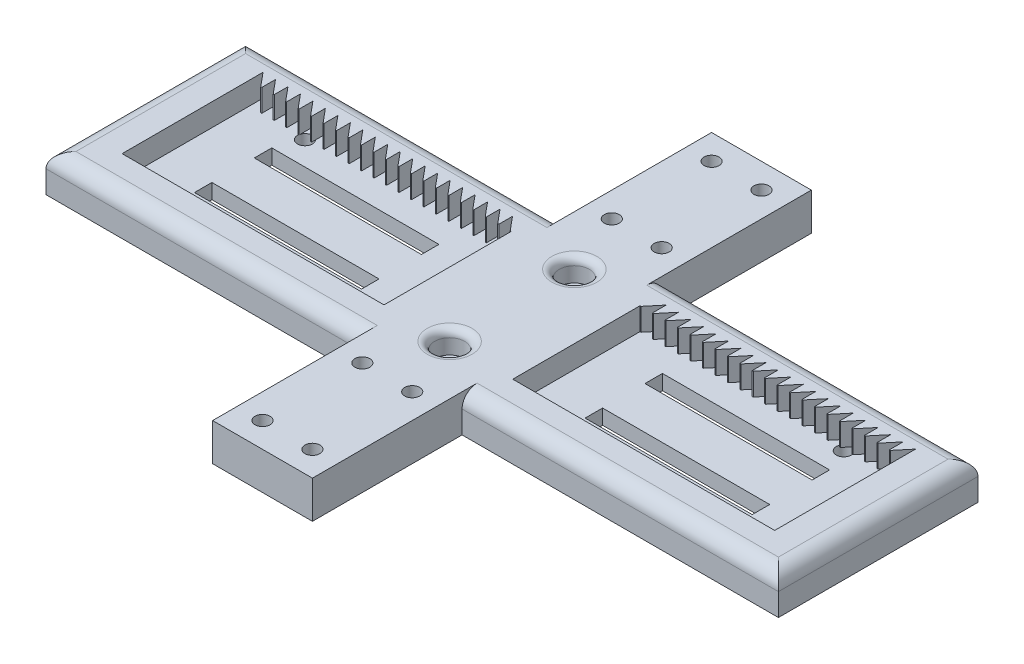
SolidWorks part; units mm, degrees
ref_plane "Front Plane" through (0, 0, 0) normal (0, 0, 1) x (1, 0, 0)
ref_plane "Top Plane" through (0, 0, 0) normal (0, 1, 0) x (1, 0, 0)
ref_plane "Right Plane" through (0, 0, 0) normal (1, 0, 0) x (0, 0, -1)
sketch "Sketch2" plane through (0, 0, 0) normal (0, 1, 0) x (1, 0, 0)
  line L0 (-12.9, 12.5) -> (-15.4, 15.5)
  line L2 (-73.4, 20) -> (-73.4, -20)
  line L5 (-65.4, 12.75) -> (-12.9, 12.75)
  line L6 (-65.4, 12.75) -> (-65.4, -12.75)
  line L7 (-65.4, -12.75) -> (-12.9, -12.75)
  line L8 (-12.9, 12.75) -> (-12.9, -12.75)
  line L9 (-73.4, 0) -> (-65.4, 0) construction
  line L10 (-15.4, 15.5) -> (-15.4, 12.5)
  line L11 (-15.4, 12.5) -> (-17.9, 15.5)
  line L12 (-17.9, 15.5) -> (-17.9, 12.5)
  line L13 (-17.9, 12.5) -> (-20.4, 15.5)
  line L14 (-20.4, 15.5) -> (-20.4, 12.5)
  line L15 (-20.4, 12.5) -> (-22.9, 15.5)
  line L16 (-22.9, 15.5) -> (-22.9, 12.5)
  line L17 (-22.9, 12.5) -> (-25.4, 15.5)
  line L18 (-25.4, 15.5) -> (-25.4, 12.5)
  line L19 (-25.4, 12.5) -> (-27.9, 15.5)
  line L20 (-27.9, 15.5) -> (-27.9, 12.5)
  line L21 (-27.9, 12.5) -> (-30.4, 15.5)
  line L22 (-30.4, 15.5) -> (-30.4, 12.5)
  line L23 (-30.4, 12.5) -> (-32.9, 15.5)
  line L24 (-32.9, 15.5) -> (-32.9, 12.5)
  line L25 (-32.9, 12.5) -> (-35.4, 15.5)
  line L26 (-35.4, 15.5) -> (-35.4, 12.5)
  line L27 (-35.4, 12.5) -> (-37.9, 15.5)
  line L28 (-37.9, 15.5) -> (-37.9, 12.5)
  line L29 (-37.9, 12.5) -> (-40.4, 15.5)
  line L30 (-40.4, 15.5) -> (-40.4, 12.5)
  line L31 (-40.4, 12.5) -> (-42.9, 15.5)
  line L32 (-42.9, 15.5) -> (-42.9, 12.5)
  line L33 (-42.9, 12.5) -> (-45.4, 15.5)
  line L34 (-45.4, 15.5) -> (-45.4, 12.5)
  line L35 (-45.4, 12.5) -> (-47.9, 15.5)
  line L36 (-47.9, 15.5) -> (-47.9, 12.5)
  line L37 (0, 0) -> (0, 9.3891) construction
  line L38 (0, -20) -> (0, 20)
  line L39 (-52.9, -12.75) -> (-52.9, -5.7094) construction
  line L41 (-25.4, 12.75) -> (-25.4, -12.75) construction
  line L45 (3.0979, 0) -> (12.9, 0) construction
  line L46 (-47.9, 12.5) -> (-50.4, 15.5)
  line L47 (-50.4, 15.5) -> (-50.4, 12.5)
  line L48 (-50.4, 12.5) -> (-52.9, 15.5)
  line L49 (-52.9, 15.5) -> (-52.9, 12.5)
  line L50 (-52.9, 12.5) -> (-55.4, 15.5)
  line L51 (-55.4, 15.5) -> (-55.4, 12.5)
  line L52 (-55.4, 12.5) -> (-57.9, 15.5)
  line L53 (-57.9, 15.5) -> (-57.9, 12.5)
  line L54 (-57.9, 12.5) -> (-60.4, 15.5)
  line L55 (-60.4, 15.5) -> (-60.4, 12.5)
  line L56 (-60.4, 12.5) -> (-62.9, 15.5)
  line L57 (-62.9, 15.5) -> (-62.9, 12.5)
  line L58 (-62.9, 12.5) -> (-65.4, 15.5)
  line L59 (-65.4, 15.5) -> (-65.4, 12.5)
  line L60 (-73.4, 20) -> (0, 20)
  line L61 (-73.4, -20) -> (0, -20)
  line L74 (0, 20) -> (0, -20) construction
  line L75 (-12.9, 0) -> (0, 0) construction
  line L76 (0, 0) -> (12.9, 0) construction
  point P5 (-73.4, 0)
  dimension "D2" = 40
  dimension "D3" = 12.5
  dimension "D4" = 25.4
  dimension "D5" = 12.5
  dimension "D6" = 2.5
  dimension "D7" = 3
  dimension "D8" = 25.5
  dimension "D9" = 12.5
  dimension "D10" = 8
  dimension "D11" = 52.9
  dimension "D15" = 21
extrude "Boss-Extrude1" add sketch "Sketch2" against normal blind 3 contours L2 L61 L38 L60
extrude "Boss-Extrude2" add sketch "Sketch2<3>" along normal blind 4.5
sketch "Sketch2<3>" plane through (0, 0, 0) normal (0, 1, 0) x (1, 0, 0) same geometry as "Sketch2"
sketch "Sketch3" plane through (0, 0, 0) normal (0, 1, 0) x (1, 0, 0)
  line L0 (-65.4, 15.5) -> (-65.4, -12.75) construction
  line L1 (-65.4, 7.75) -> (50.52, 7.75)
  line L2 (-65.4, 7.75) -> (-65.4, 4.25)
  line L3 (-65.4, 4.25) -> (50.52, 4.25)
  line L4 (50.52, 7.75) -> (50.52, 4.25)
  line L6 (-65.4, 0) -> (-44.0832, 0) construction
  line L7 (-55.9, 4.25) -> (-55.9, 7.75)
  line L8 (-22.4, 4.25) -> (-22.4, 7.75)
  line L9 (-12.9, 12.75) -> (-12.9, -12.75) construction
  line L10 (-7.44, 4.25) -> (-7.44, -3.7317) construction
  line L11 (-22.4, -4.25) -> (-22.4, -7.75)
  line L12 (-55.9, -4.25) -> (-55.9, -7.75)
  line L13 (-65.4, -4.25) -> (50.52, -4.25)
  line L14 (50.52, -7.75) -> (50.52, -4.25)
  line L15 (-65.4, -7.75) -> (50.52, -7.75)
  line L16 (-65.4, -7.75) -> (-65.4, -4.25)
  line L17 (7.52, -4.25) -> (7.52, -7.75)
  line L18 (41.02, -4.25) -> (41.02, -7.75)
  line L19 (41.02, 4.25) -> (41.02, 7.75)
  line L20 (7.52, 4.25) -> (7.52, 7.75)
  line L21 (-65.4, 15.5) -> (-65.4, -12.75) construction
  line L22 (-65.4, 15.5) -> (-65.4, -12.75)
  point P10 (-65.4, 6)
  dimension "D1" = 3.5
  dimension "D2" = 6
  dimension "D3" = 9.5
  dimension "D4" = 9.5
extrude "Cut-Extrude1" cut sketch "Sketch3" against normal through all contours L3 L8 L1 L7 | L12 L15 L11 L13 | L20 L3 L19 L1 | L18 L13 L17 L15 region at (-39.15, 0, -6) region at (24.27, 0, -6) region at (-39.15, 0, 6) region at (24.27, 0, 6)
sketch "Sketch4" plane through (0, 4.5, 0) normal (0, 1, 0) x (1, 0, 0)
  line L2 (0, 12.5) -> (0, 0) construction
  circle A0 centre (0, 12.5) radius 1.75
  circle A2 centre (54, 12.5) radius 1.75
  circle A3 centre (54, -12.5) radius 1.75
  circle A4 centre (0, -12.5) radius 1.75
  dimension "D1" = 3.5
  dimension "D2" = 2
  dimension "D3" = 12.5
  dimension "D4" = 2
extrude "Cut-Extrude3" cut sketch "Sketch4" against normal through all contours A0 | A4 | A3 | A2
sketch "Sketch5" plane through (0, 4.5, 0) normal (0, 1, 0) x (1, 0, 0)
  circle A1 centre (0, 12.5) radius 3
  circle A4 centre (0, -12.5) radius 3
extrude "Cut-Extrude4" cut sketch "Sketch5" against normal offset from surface (4.5 mm away) 3 up to face at (-39.15, -3, 6)
sketch "Sketch7" plane through (0, -3, 0) normal (0, -1, 0) x (1, 0, 0)
  circle A0 centre (-54, 12.5) radius 1.5
  circle A1 centre (-54, -12.5) radius 1.5
  arc A2 (0, -10.75) -> (0, -14.25) centre (0, -12.5) ccw construction
  arc A3 (0, 14.25) -> (0, 10.75) centre (0, 12.5) ccw construction
  arc A4 (0, -10.75) -> (0, -14.25) centre (0, -12.5) ccw
  arc A5 (0, 14.25) -> (0, 10.75) centre (0, 12.5) ccw
  point P11 (0, 0)
  point P12 (0, 0)
  dimension "D1" = 3
  dimension "D2" = 3
  dimension "D3" = 54
extrude "Cut-Extrude5" cut sketch "Sketch7" against normal blind 3 contours A0 | A1
sketch "Sketch9" plane through (0, 4.5, 0) normal (0, 1, 0) x (1, 0, 0)
  line L1 (0, 20) -> (-10, 20)
  line L2 (0, 20) -> (0, 50)
  line L3 (0, 50) -> (-10, 50)
  line L4 (-10, 20) -> (-10, 50)
  line L5 (0, -20) -> (-10, -20)
  line L6 (0, -20) -> (0, -50)
  line L7 (0, -50) -> (-10, -50)
  line L8 (-10, -20) -> (-10, -50)
  dimension "D1" = 30
  dimension "D2" = 30
  dimension "D3" = 10
  dimension "D4" = 10
extrude "Boss-Extrude3" add sketch "Sketch9" against normal up to surface (7.5 mm away) up to face at (-54, -3, 11)
sketch "Sketch10" plane through (0, 4.5, 0) normal (0, 1, 0) x (1, 0, 0)
  line L0 (0, 15.5) -> (0, 50) construction
  line L1 (0, 0) -> (-6.4734, 0) construction
  line L2 (0, -9.5) -> (0, 9.5) construction
  circle A0 centre (-5, 45) radius 1.5
  circle A1 centre (-5, 25) radius 1.5
  circle A2 centre (-5, -45) radius 1.5
  circle A3 centre (-5, -25) radius 1.5
  point P15 (0, 0)
  dimension "D1" = 3
  dimension "D3" = 3
  dimension "D2" = 5
  dimension "D4" = 5
  dimension "D5" = 20
  dimension "D6" = 25
extrude "Cut-Extrude6" cut sketch "Sketch10" against normal blind 6 contours A1 | A3 | A2 | A0 region at (-5, 4.5, -25) region at (-5, 4.5, 45) region at (-5, 4.5, 25)
mirror "Mirror1" about plane through (0, 0, 0) normal (1, 0, 0) of bodies 110 106
fillet "Fillet2" radius 3 6 edges at (73.4, 4.5, 0) (41.7, 4.5, -20) (41.7, 4.5, 20) (-73.4, 4.5, 0) (-41.7, 4.5, 20) (-41.7, 4.5, -20)
fillet "Fillet3" radius 1.5 2 edges at (0, 4.5, 15.5) (0, 4.5, -9.5)
